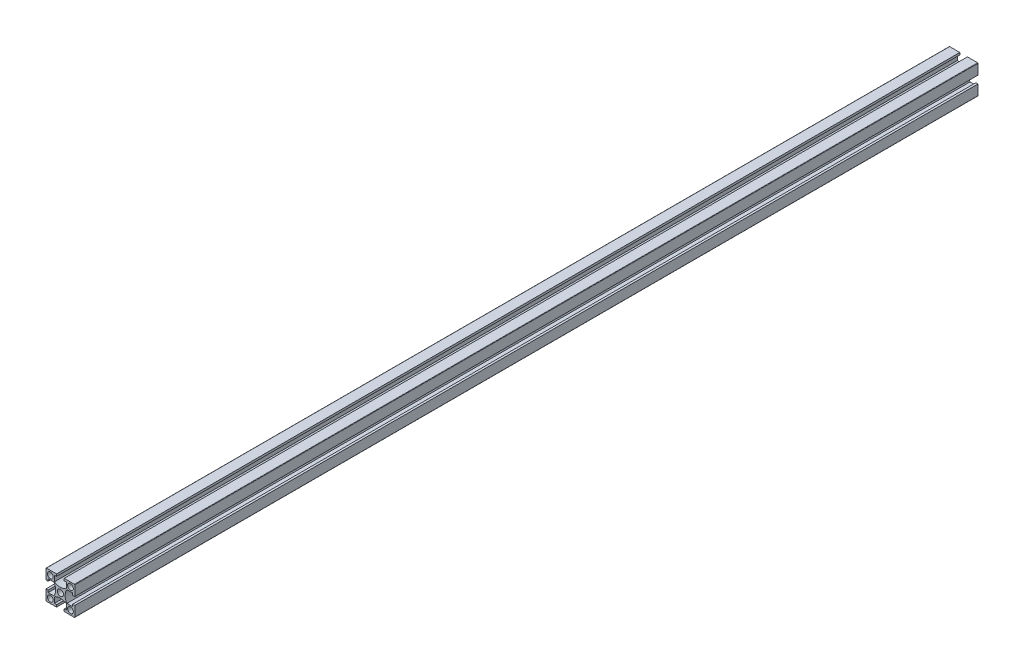
SolidWorks part; units mm, degrees
material "3.0255 (EN-AW 1350A)"
ref_plane "정면" through (0, 0, 0) normal (0, 0, 1) x (1, 0, 0)
ref_plane "윗면" through (0, 0, 0) normal (0, 1, 0) x (1, 0, 0)
ref_plane "우측면" through (0, 0, 0) normal (1, 0, 0) x (0, 0, -1)
sketch "스케치1" plane through (0, 0, 0) normal (0, 0, 1) x (1, 0, 0)
  line L0 (0, 32.0265) -> (0, -31.6588) construction
  line L1 (-10, 10) -> (-10, -10)
  line L2 (-10, 10) -> (10, 10)
  line L3 (-10, 2.65) -> (-8.5, 2.65)
  line L4 (13.6618, 0) -> (-11.6993, 0) construction
  line L5 (-8.5, 2.65) -> (-8.5, 4.15)
  line L6 (-8.5, 4.15) -> (-4.5032, 4.15)
  line L7 (-10, -2.65) -> (-8.5, -2.65)
  line L8 (-8.5, -2.65) -> (-8.5, -4.15)
  line L9 (-8.5, -4.15) -> (-4.5032, -4.15)
  line L10 (-10, -10) -> (10, -10)
  line L11 (10, 10) -> (10, -10)
  circle A0 centre (-7, 7) radius 2
  circle A1 centre (-7, -7) radius 2
  arc A2 (-4.5032, 4.15) -> (-4.5032, -4.15) centre (-11.0587, 0) cw
  circle A3 centre (0, 0) radius 2.15
  circle A4 centre (7, 7) radius 2
  circle A5 centre (7, -7) radius 2
  point P21 (-10, 0)
  point P23 (-3.3, 0)
  point P31 (0, -10)
  point P32 (0, 10)
  dimension "D3" = 4
  dimension "D9" = 6.7
  dimension "D10" = 4.3
  dimension "D11" = 7.7587
  dimension "D1" = 20
  dimension "D2" = 20
  dimension "D4" = 14
  dimension "D5" = 14
  dimension "D6" = 5.3
  dimension "D7" = 8.3
  dimension "D8" = 1.5
extrude "보스-돌출1" add sketch "스케치1" along normal blind 628 contours A0 | A4 | A3 | A5 | A1 | A2 L6 L5 L3 L1 L7 L8 L9 | L2 L11 L10 L1 region at (-6.6069, 0, 0) region at (-7, 7, 0) region at (-7, -7, 0) region at (0, 0, 0) region at (7, 7, 0) region at (7, -7, 0)
extrude "컷-돌출1" cut sketch "스케치1<3>" along normal up to next contours A2 L6 L5 L3 L1 L7 L8 L9 region at (-6.6069, 0, 0)
sketch "스케치1<3>" plane through (0, 0, 0) normal (0, 0, 1) x (1, 0, 0) same geometry as "스케치1"
pattern_circular "원형 패턴1" count 4 over 360 about axis through (0, 0, 628) along (0, 0, -1) of "컷-돌출1" reverse direction yes
fillet "필렛1" radius 0.3 4 edges at (10, -10, 314) (-10, -10, 314) (-10, 10, 314) (10, 10, 314)
sketch "스케치2" plane through (0, 0, 0) normal (1, 0, 0) x (0, 0, -1)
  line L2 (0, -2.65) -> (0, -9.7) construction
  circle A0 centre (-15, 0) radius 2.5
  dimension "D2" = 5
  dimension "D1" = 15
extrude "컷-돌출2" cut sketch "스케치2" against normal through all both and the other way through all
sketch "스케치3" plane through (0, -10, 0) normal (0, -1, 0) x (1, 0, 0)
  line L0 (9.7, 131) -> (-9.7, 131) construction
  line L1 (9.7, 0) -> (9.7, 628) construction
  line L2 (-9.7, 628) -> (-9.7, 0) construction
  line L3 (-9.7, 0) -> (-2.65, 0) construction
  line L4 (9.7, 367) -> (-9.7, 367) construction
  circle A0 centre (0, 141) radius 2.5
  circle A1 centre (0, 357) radius 2.5
  dimension "D1" = 141
  dimension "D4" = 10
  dimension "D2" = 131
  dimension "D3" = 236
extrude "컷-돌출3" cut sketch "스케치3" against normal through all
sketch "스케치5" plane through (0, -10, 0) normal (0, -1, 0) x (1, 0, 0)
  line L0 (-9.7, 485) -> (9.7, 485) construction
  line L1 (-9.7, 628) -> (-9.7, 0) construction
  line L2 (9.7, 0) -> (9.7, 628) construction
  line L3 (-9.7, 433) -> (9.7, 433) construction
  line L4 (-9.7, 295) -> (9.7, 295) construction
  line L5 (-9.7, 248.9) -> (9.7, 248.9) construction
  line L6 (-9.7, 423) -> (9.7, 423) construction
  line L7 (-9.7, 196.9) -> (9.7, 196.9) construction
  line L8 (2.65, 628) -> (9.7, 628) construction
  line L9 (-9.7, 628) -> (-2.65, 628) construction
  line L10 (-9.7, 74.15) -> (9.7, 74.15) construction
  line L11 (-9.7, 2.15) -> (9.7, 2.15) construction
  line L12 (-9.7, 475) -> (9.7, 475) construction
  line L13 (-9.7, 305) -> (9.7, 305) construction
  line L14 (-9.7, 238.9) -> (9.7, 238.9) construction
  line L15 (-9.7, 186.9) -> (9.7, 186.9) construction
  line L16 (-9.7, 64.15) -> (9.7, 64.15) construction
  line L17 (-9.7, 12.15) -> (9.7, 12.15) construction
  circle A0 centre (0, 475) radius 2.15
  circle A2 centre (0, 423) radius 2.15
  circle A3 centre (0, 305) radius 2.12
  circle A4 centre (0, 238.9) radius 2.15
  circle A5 centre (0, 186.9) radius 2.15
  circle A6 centre (0, 64.15) radius 2.15
  circle A7 centre (0, 12.15) radius 2.15
  dimension "D15" = 4.3
  dimension "D1" = 143
  dimension "D2" = 195
  dimension "D3" = 333
  dimension "D4" = 379.1
  dimension "D5" = 431.1
  dimension "D6" = 553.85
  dimension "D7" = 625.85
  dimension "D8" = 10
  dimension "D9" = 10
  dimension "D10" = 10
  dimension "D11" = 10
  dimension "D12" = 10
  dimension "D13" = 10
  dimension "D14" = 10
extrude "컷-돌출5" cut sketch "스케치5" against normal through all
